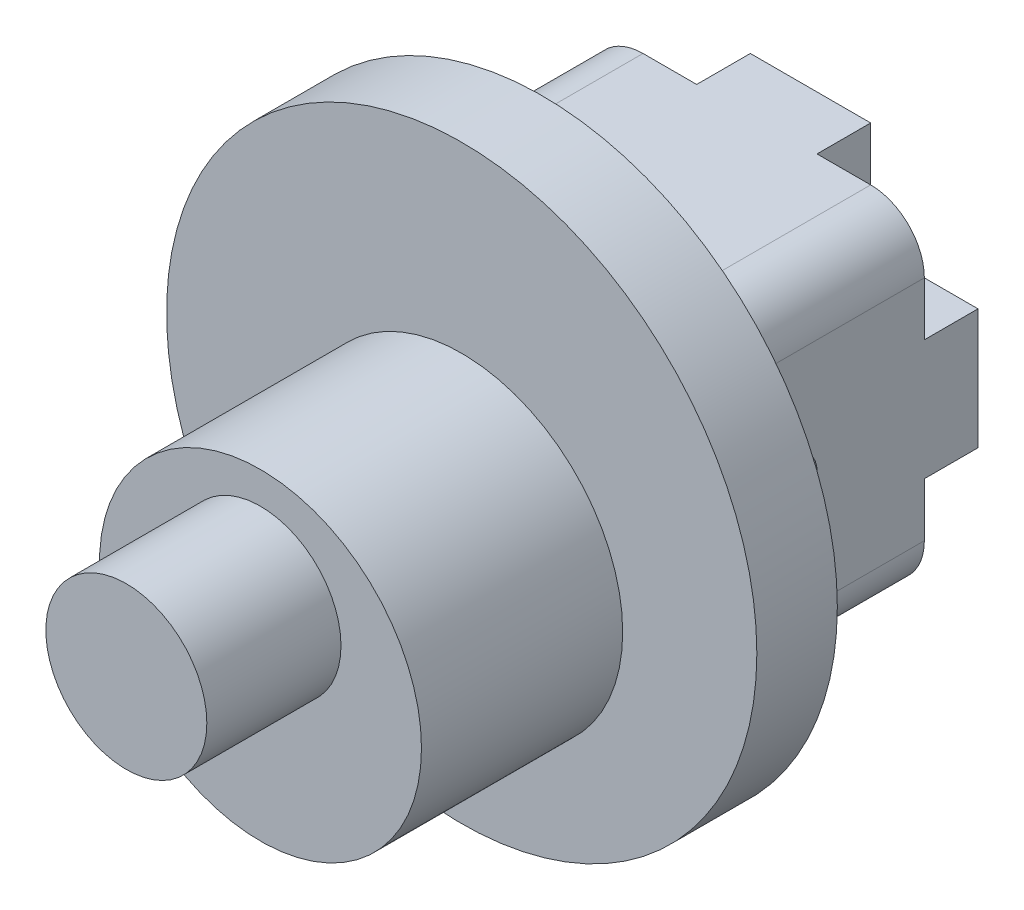
SolidWorks part; units mm, degrees
material "ABS PC"
ref_plane "Front Plane" through (0, 0, 0) normal (0, 0, 1) x (1, 0, 0)
ref_plane "Top Plane" through (0, 0, 0) normal (0, 1, 0) x (1, 0, 0)
ref_plane "Right Plane" through (0, 0, 0) normal (1, 0, 0) x (0, 0, -1)
sketch "Sketch1" plane through (0, 0, 0) normal (0, 0, 1) x (1, 0, 0)
  line L0 (4.2426, 6.2426) -> (-4.2426, 6.2426)
  line L1 (6.2426, 4.2426) -> (6.2426, -4.2426)
  line L2 (4.2426, -6.2426) -> (-4.2426, -6.2426)
  line L3 (-6.2426, 4.2426) -> (-6.2426, -4.2426)
  line L4 (2.2426, 4.2426) -> (2.2426, 6.2426)
  line L5 (4.2426, 2.2426) -> (6.2426, 2.2426)
  line L6 (4.2426, -2.2426) -> (6.2426, -2.2426)
  line L7 (2.2426, -4.2426) -> (2.2426, -6.2426)
  line L8 (-2.2426, -4.2426) -> (-2.2426, -6.2426)
  line L9 (-4.2426, -2.2426) -> (-6.2426, -2.2426)
  line L10 (-4.2426, 2.2426) -> (-6.2426, 2.2426)
  line L11 (-2.2426, 4.2426) -> (-2.2426, 6.2426)
  circle A0 centre (-4.2426, 4.2426) radius 2
  circle A4 centre (4.2426, 4.2426) radius 2
  circle A5 centre (4.2426, -4.2426) radius 2
  circle A6 centre (-4.2426, -4.2426) radius 2
  point P13 (0, 0)
  dimension "D1" = 4
  dimension "D2" = 4
extrude "Boss-Extrude1" add sketch "Sketch1" along normal blind 2 contours A5 A0 region at (0, 0, 0)
sketch "Sketch3" plane through (0, 0, 10) normal (0, 0, 1) x (1, 0, 0)
  circle A0 centre (0, 0) radius 11
  dimension "D1" = 22
extrude "Boss-Extrude3" add sketch "Sketch3" along normal blind 3
sketch "Sketch4" plane through (0, 0, 13) normal (0, 0, 1) x (1, 0, 0)
  circle A0 centre (0, -1.812) radius 6
  dimension "D1" = 12
  dimension "D2" = 1.812
extrude "Boss-Extrude4" add sketch "Sketch4" along normal blind 7.5
sketch "Sketch5" plane through (0, 0, 20.5) normal (0, 0, 1) x (1, 0, 0)
  circle A0 centre (0, 0) radius 3
  dimension "D1" = 6
extrude "Boss-Extrude5" add sketch "Sketch5" along normal blind 5
extrude "Boss-Extrude6" add sketch "Sketch1<4>" along normal blind 8 from offset 2 contours A4 | A0 | A6 L8 L2 L7 A5 L6 L1 L5 A4 L4 L0 L11 A0 L10 L3 L9 | A0 L11 L0 | A0 L3 L10 | A6 L9 L3 | A6 L2 L8 | A5 L7 L2 | A5 | A5 L1 L6 | A4 L5 L1 | A4 L0 L4 | A6 region at (2.6894, 5.7959, 0) region at (4.2426, 4.2426, 0) region at (0, 0, 0) region at (5.7959, 2.6894, 0) region at (-2.6894, 5.7959, 0) region at (-4.2426, 4.2426, 0) region at (5.7959, -2.6894, 0) region at (-5.7959, 2.6894, 0) region at (4.2426, -4.2426, 0) region at (2.6894, -5.7959, 0) region at (-5.7959, -2.6894, 0) region at (-2.6894, -5.7959, 0)
sketch "Sketch1<4>" plane through (0, 0, 0) normal (0, 0, 1) x (1, 0, 0) same geometry as "Sketch1"
sketch "Sketch7" plane through (6.2426, 0, 0) normal (1, 0, 0) x (0, 0, -1)
  line L0 (-10, 4.2426) -> (-10, -4.2426) construction
  circle A0 centre (-7, 0) radius 1
  dimension "D2" = 2
  dimension "D1" = 3
extrude "Cut-Extrude2" cut sketch "Sketch7" against normal blind 15
